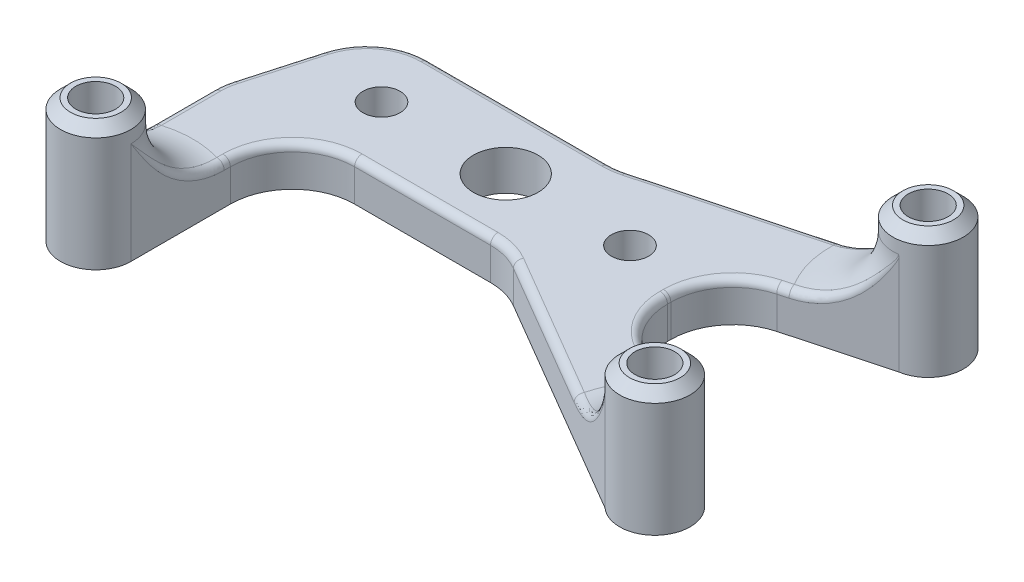
SolidWorks part; units mm, degrees
ref_plane "Front Plane" through (0, 0, 0) normal (0, 0, 1) x (1, 0, 0)
ref_plane "Top Plane" through (0, 0, 0) normal (0, 1, 0) x (1, 0, 0)
ref_plane "Right Plane" through (0, 0, 0) normal (1, 0, 0) x (0, 0, -1)
sketch "Sketch6" plane through (0, 0, 0) normal (0, 1, 0) x (1, 0, 0)
  line L1 (-19.05, -6.35) -> (19.05, -6.35)
  line L2 (-19.05, -6.35) -> (-19.05, 6.35)
  line L3 (-19.05, 6.35) -> (19.05, 6.35)
  line L4 (19.05, -6.35) -> (19.05, 6.35)
  line L5 (-19.05, -6.35) -> (19.05, 6.35) construction
  line L6 (-19.05, 6.35) -> (19.05, -6.35) construction
  point P0 (0, 0)
  dimension "D1" = 12.7
  dimension "D2" = 38.1
extrude "Boss-Extrude6" add sketch "Sketch6" along normal blind 3.175 separate body
sketch "Sketch4" plane through (0, 0, 0) normal (0, 1, 0) x (1, 0, 0)
  circle A0 centre (-19.05, -22.86) radius 3.6
  circle A1 centre (33.02, -17.78) radius 3.6
  circle A2 centre (33.02, 10.16) radius 3.6
  dimension "D1" = 7.2
  dimension "D2" = 7.2
  dimension "D3" = 7.2
  dimension "D4" = 52.07
  dimension "D5" = 5.08
  dimension "D6" = 27.94
  dimension "D7" = 10.16
  dimension "D8" = 33.02
extrude "Boss-Extrude5" add sketch "Sketch4" along normal blind 12.7
sketch "Sketch8" plane through (0, 0, 0) normal (0, 1, 0) x (1, 0, 0)
  line L2 (31.8384, 13.5606) -> (5.0632, 6.35)
  line L3 (19.05, 6.35) -> (-19.05, 6.35) construction
  line L4 (33.5862, 6.6048) -> (19.05, 2.6902)
  line L5 (19.05, -6.35) -> (19.05, 6.35) construction
  line L6 (19.05, 2.6902) -> (19.05, -6.35)
  line L7 (19.05, -6.35) -> (34.6277, -14.5589)
  line L8 (30.6114, -20.4556) -> (6.515, -6.35)
  line L9 (-19.05, -6.35) -> (19.05, -6.35) construction
  line L10 (6.515, -6.35) -> (-15.45, -6.35)
  line L11 (-15.45, -6.35) -> (-15.45, -22.86)
  line L12 (-22.65, -22.86) -> (-22.65, -6.35)
  line L13 (-22.65, -6.35) -> (-19.05, 6.35)
  line L14 (-19.05, 6.35) -> (5.0632, 6.35)
  circle A0 centre (33.02, 10.16) radius 3.6 construction
  arc A1 (33.5862, 6.6048) -> (31.8384, 13.5606) centre (33.02, 10.16) ccw
  circle A2 centre (33.02, -17.78) radius 3.6 construction
  arc A3 (34.6277, -14.5589) -> (30.6114, -20.4556) centre (33.02, -17.78) cw
  circle A4 centre (-19.05, -22.86) radius 3.6 construction
  arc A5 (-15.45, -22.86) -> (-22.65, -22.86) centre (-19.05, -22.86) cw
extrude "Boss-Extrude7" add sketch "Sketch8" along normal blind 4.064
fillet "Fillet1" radius 6.35 7 edges at (-15.45, 2.032, 6.35) (6.515, 2.032, 6.35) (19.05, 2.032, 6.35) (19.05, 2.032, -2.6902) (5.0632, 2.032, -6.35) (-22.65, 2.032, 6.35) (-19.05, 2.032, -6.35)
sketch "Sketch9" plane through (0, 4.064, 0) normal (0, 1, 0) x (1, 0, 0)
  circle A0 centre (-12.7, 0) radius 1.905
  circle A1 centre (12.7, 0) radius 1.905
  circle A2 centre (0, 0) radius 3.302
  dimension "D3" = 3.81
  dimension "D4" = 3.81
  dimension "D5" = 6.604
  dimension "D1" = 25.4
  dimension "D2" = 12.7
extrude "Cut-Extrude3" cut sketch "Sketch9" against normal through all
fillet "Fillet2" radius 6.35 3 edges at (-19.05, 4.064, 19.26) (30.0446, 4.064, 15.7534) (29.5285, 4.064, -9.2827)
sketch "Sketch10" plane through (0, 12.7, 0) normal (0, 1, 0) x (1, 0, 0)
  circle A0 centre (-19.05, -22.86) radius 2.032
  circle A1 centre (33.02, -17.78) radius 2.032
  circle A2 centre (33.02, 10.16) radius 2.032
  dimension "D1" = 4.064
  dimension "D2" = 4.064
  dimension "D3" = 4.064
extrude "Cut-Extrude4" cut sketch "Sketch10" against normal blind 4.7752
chamfer "Chamfer1" distance 1.016 angle 45 3 edges at (33.02, 12.7, -6.56) (33.02, 12.7, 21.38) (-19.05, 12.7, 26.46)
fillet "Fillet3" radius 0.762 23 edges at (34.1822, 9.6509, 14.3242) (24.4655, 4.064, 9.2038) (33.042, 9.2814, -6.4582) (24.3677, 4.064, -4.1223) (20.3598, 4.064, -1.6865) (19.05, 4.064, 2.3472) (30.8667, 8.8079, -13.2989) (14.5002, 4.064, -8.8914) (5.0559, 4.064, -6.4048) (-22.65, 5.6615, 18.3911) (-22.65, 4.064, 10.4084) (-22.5895, 4.064, 6.3584) (-21.3842, 4.064, 1.8845) (-18.079, 4.064, -5.0655) (-15.45, 5.6615, 18.3911) (-15.45, 4.064, 13.142) (-13.5901, 4.064, 8.2099) (29.7882, 8.4666, 19.9737) (15.605, 4.064, 11.6711) (6.455, 4.064, 6.5713) (19.9631, 4.064, 5.7991) (-5.0133, 4.064, -6.35) (-2.1535, 4.064, 6.35)
sketch "Sketch11" plane through (0, 7.9248, 0) normal (0, 1, 0) x (1, 0, 0)
  circle A0 centre (-19.05, -22.86) radius 1.5875
  circle A1 centre (33.02, -17.78) radius 1.5875
  circle A2 centre (33.02, 10.16) radius 1.5875
  dimension "D1" = 3.175
  dimension "D2" = 3.175
  dimension "D3" = 3.175
extrude "Cut-Extrude5" cut sketch "Sketch11" against normal through all
